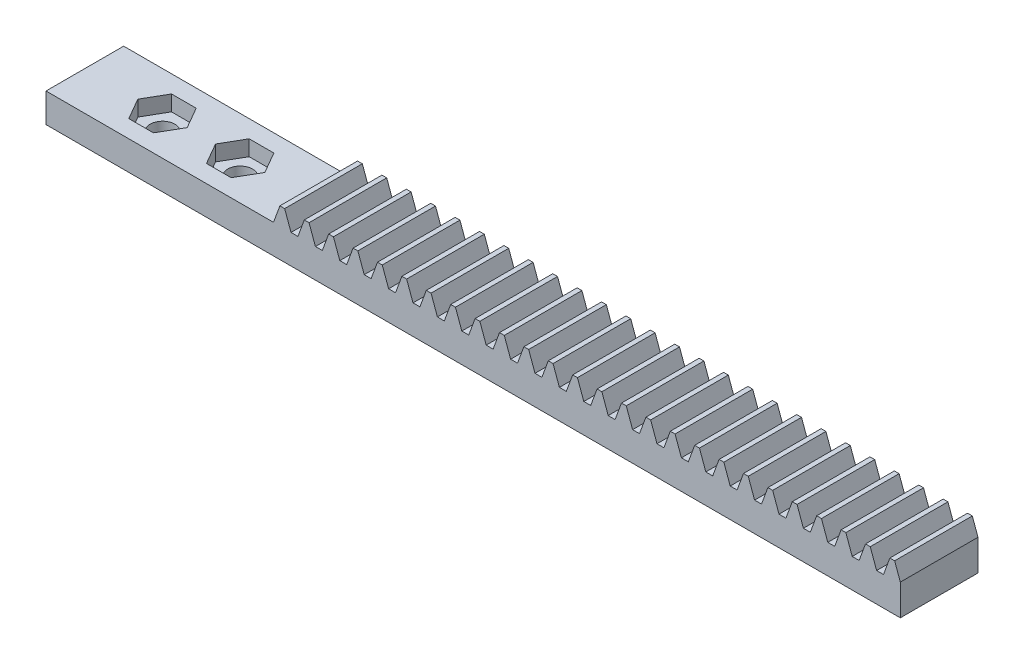
SolidWorks part; units mm, degrees
extrude "Blank" add sketch "BlankSke" against normal blind 10
sketch "BlankSke" plane through (0, 0, 0) normal (0, 0, 1) x (1, 0, 0)
  line L1 (0, 0) -> (100, 0)
  line L2 (0, 0) -> (0, 6)
  line L3 (0, 6) -> (100, 6)
  line L4 (100, 0) -> (100, 6)
  dimension "Length" = 100
ref_plane "Plane1" through (0, 0, 0) normal (0, 0, 1) x (1, 0, 0)
ref_plane "Plane2" through (0, 0, 0) normal (0, 1, 0) x (1, 0, 0)
ref_plane "Plane3" through (0, 0, 0) normal (1, 0, 0) x (0, 0, -1)
other "Configuration Table"
sketch "HoldingSke" plane through (0, 0, 0) normal (0, 1, 0) x (1, 0, 0)
  line L0 (0, 0) -> (0.1392, 0.9903)
  line L1 (-15, 0) -> (100, 0) construction
  line L2 (0, 0) -> (-2.1039, 2.3779)
  line L3 (0, 0) -> (-11.863, 4.5341)
  line L4 (0, 0) -> (7.2428, 4.7035)
  line L5 (0, 0) -> (-23.7986, -8.8762)
  line L6 (0, 0) -> (-10.5278, -7.1032)
  line L9 (-71.009, 38.7566) -> (22.9603, 72.9586)
  line L10 (-76.2, 3.3779) -> (-71.2, 3.3779)
  line L11 (0, 0) -> (-10, 0)
  line L12 (-76.2, 101.6) -> (-76.162, 101.6)
  line L13 (24.9733, 27.94) -> (52.9518, 28.4284)
  line L14 (24.9733, 27.94) -> (24.9743, 27.94)
  line L15 (24.9733, 27.94) -> (100.4006, 29.5858)
  circle A0 centre (0, 0) radius 19.05
  circle A1 centre (0, 0) radius 2.5
  circle A2 centre (0, 0) radius 12.7
  dimension "Num_teeth" = 33
  dimension "Width" = 10
  dimension "Length" = 100
  dimension "Pitch_height" = 5
sketch "TooCutSkeIll" plane through (0, 0, 0) normal (0, 0, 1) x (1, 0, 0)
  line L0 (-1.2538, 5.9737) -> (-0.5045, 3.9152)
  line L1 (-0.2687, 3.75) -> (0.2687, 3.75)
  line L2 (0.5045, 3.9152) -> (1.2538, 5.9737)
  line L3 (100, 6) -> (0, 6) construction
  line L4 (0, 0) -> (0, 64.897) construction
  line L5 (-13.208, 5) -> (12.954, 5) construction
  line L6 (0, 0) -> (100, 0) construction
  line L7 (0.8994, 5) -> (0.8994, 48.7463) construction
  line L8 (-0.8994, 5) -> (-0.8994, 48.7463) construction
  line L9 (1.2914, 6) -> (1.2914, 6.0254)
  line L10 (-1.2914, 6) -> (-1.2914, 6.0254)
  line L11 (-1.2914, 6.0254) -> (1.2914, 6.0254)
  arc A0 (0.2687, 3.75) -> (0.5045, 3.9152) centre (0.2687, 4.001) ccw
  arc A1 (-0.5045, 3.9152) -> (-0.2687, 3.75) centre (-0.2687, 4.001) ccw
  arc A2 (1.2914, 6) -> (1.2538, 5.9737) centre (1.2914, 5.96) ccw
  arc A3 (-1.2538, 5.9737) -> (-1.2914, 6) centre (-1.2914, 5.96) ccw
  dimension "Addendum_plus" = 1.0254
  dimension "Pitch_height" = 5
  dimension "Pressure_angle" = 20
  dimension "Gap_width" = 1.7988
  dimension "Dedendum" = 1.25
extrude "ToothCutIll" [suppressed] cut sketch "TooCutSkeIll" against normal through all
sketch "TooCutSkeSim" plane through (0, 0, 0) normal (0, 0, 1) x (1, 0, 0)
  line L0 (0.4444, 3.75) -> (-0.4444, 3.75)
  line L1 (1.2726, 6.0254) -> (0.4444, 3.75)
  line L2 (0, 17.4625) -> (0, 53.467) construction
  line L3 (1.2726, 6.0254) -> (-1.2726, 6.0254)
  line L6 (-1.2726, 6.0254) -> (-0.4444, 3.75)
  line L9 (-0.8994, 5) -> (0.8994, 5) construction
  line L10 (0, 0) -> (100, 0) construction
  line L11 (0.8994, 5) -> (0.8994, 53.467) construction
  line L12 (-0.8994, 5) -> (-0.8994, 53.467) construction
  dimension "Addendum_plus" = 1.0254
  dimension "Pitch_height" = 5
  dimension "Pressure_angle" = 20
  dimension "Gap_width" = 1.7988
  dimension "Dedendum" = 1.25
extrude "ToothCutSim" cut sketch "TooCutSkeSim" against normal through all
pattern_linear "TeethCuts" count 33 spacing 3.1416 along (1, 0, 0) of "ToothCutIll", "ToothCutSim"
sketch "草图1" plane through (0, 0, 0) normal (0, 0, 1) x (1, 0, 0)
  line L1 (0, 3.75) -> (19.294, 3.75)
  line L2 (0, 3.75) -> (0, 13.2211)
  line L3 (0, 13.2211) -> (19.294, 13.2211)
  line L4 (19.294, 3.75) -> (19.294, 13.2211)
extrude "切除-拉伸1" cut sketch "草图1" against normal blind 10
sketch "草图2" plane through (0, 0, 0) normal (-1, 0, 0) x (0, 0, 1)
  line L1 (-10, 3.75) -> (0, 3.75)
  line L2 (-10, 3.75) -> (-10, 0)
  line L3 (-10, 0) -> (0, 0)
  line L4 (0, 3.75) -> (0, 0)
extrude "凸台-拉伸1" add sketch "草图2" along normal blind 10
sketch "草图3" plane through (0, 3.75, 0) normal (0, 1, 0) x (1, 0, 0)
  line L0 (-10, 5) -> (19.294, 5) construction
  line L1 (-10, 0) -> (-10, 10) construction
  line L2 (19.294, 10) -> (19.294, 0) construction
  circle A0 centre (0, 5) radius 1.6
  circle A1 centre (10, 5) radius 1.6
  dimension "D1" = 3.2
  dimension "D2" = 10
  dimension "D3" = 3.2
  dimension "D4" = 10
extrude "切除-拉伸2" cut sketch "草图3" against normal blind 10
sketch "草图4" plane through (0, 3.75, 0) normal (0, 1, 0) x (1, 0, 0)
  line L1 (-1.5877, 7.75) -> (-3.1754, 5)
  line L2 (-3.1754, 5) -> (-1.5877, 2.25)
  line L3 (-1.5877, 2.25) -> (1.5877, 2.25)
  line L4 (1.5877, 2.25) -> (3.1754, 5)
  line L5 (3.1754, 5) -> (1.5877, 7.75)
  line L6 (1.5877, 7.75) -> (-1.5877, 7.75)
  line L7 (8.4123, 7.75) -> (6.8246, 5)
  line L8 (6.8246, 5) -> (8.4123, 2.25)
  line L9 (8.4123, 2.25) -> (11.5877, 2.25)
  line L10 (11.5877, 2.25) -> (13.1754, 5)
  line L11 (13.1754, 5) -> (11.5877, 7.75)
  line L12 (11.5877, 7.75) -> (8.4123, 7.75)
  circle A0 centre (0, 5) radius 2.75 construction
  circle A1 centre (10, 5) radius 2.75 construction
  dimension "D1" = 5.5
  dimension "D2" = 5.5
extrude "切除-拉伸3" cut sketch "草图4" against normal blind 2
equation "' \"Module@HoldingSke\" = 6.35"
equation "' \"Num_teeth@HoldingSke\" = 12"
equation "' \"Ap@HoldingSke\" =  20"
equation "' \"Ap@HoldingSke\" = 20"
equation "' \"Width@HoldingSke\" = 0.25 * 25.4"
equation "' \"Show_teeth@HoldingSke\" = 500"
equation "' \"Backlash@HoldingSke\" = 0.009 * 25.4"
equation "' \"Addendum_fac@HoldingSke\" = 1.0"
equation "' \"Dedendum_fac@HoldingSke\" = 1.25"
equation "' \"Dedendum_add@HoldingSke\" = 0.00005 * 25.4"
equation "' \"Clearance_fac@HoldingSke\" = 0.25"
equation "' \"Pitch_height@HoldingSke\" = 1 * 25.4"
equation "' \"Length@HoldingSke\" = 4.71 * 25.4"
equation "\"Pitch@HoldingSke\" = 1 / \"Module@HoldingSke\""
equation "\"MPH@HoldingSke\" = \"Dedendum_fac@HoldingSke\" / \"Pitch@HoldingSke\" + 2 * \"Dedendum_add@HoldingSke\" + 0.002 * 25.4"
equation "\"MPH@HoldingSke\" = ((sgn( \"MPH@HoldingSke\" - \"Pitch_height@HoldingSke\")+1)*( \"MPH@HoldingSke\" - \"Pitch_height@HoldingSke\"))/2 + \"Pitch_height@HoldingSke\""
equation "\"Blank_height@BlankSke\" = \"Pitch_height@HoldingSke\" + \"Addendum_fac@HoldingSke\"  / \"Pitch@HoldingSke\" "
equation "\"Length@BlankSke\" =  \"Length@HoldingSke\""
equation "\"Face_width@Blank\" = \"Width@HoldingSke\""
equation "\"Pressure_angle@TooCutSkeIll\" = \"Ap@HoldingSke\""
equation "\"Addendum_plus@TooCutSkeIll\" =  \"Addendum_fac@HoldingSke\"  / \"Pitch@HoldingSke\" + 0.001 *25.4"
equation "\"Dedendum@TooCutSkeIll\" = \"Dedendum_fac@HoldingSke\"  / \"Pitch@HoldingSke\""
equation "\"Pitch_height@TooCutSkeIll\" =  \"MPH@HoldingSke\""
equation "\"Gap_width@TooCutSkeIll\" = 3.14159265 / 2 / \"Pitch@HoldingSke\" + 6 * \"Backlash@HoldingSke\""
equation "\"Pressure_angle@TooCutSkeSim\" = \"Ap@HoldingSke\""
equation "\"Addendum_plus@TooCutSkeSim\" =  \"Addendum_fac@HoldingSke\"  / \"Pitch@HoldingSke\" + 0.001 * 25.4"
equation "\"Dedendum@TooCutSkeSim\" = \"Dedendum_fac@HoldingSke\"  / \"Pitch@HoldingSke\""
equation "\"Pitch_height@TooCutSkeSim\" =  \"MPH@HoldingSke\""
equation "\"Gap_width@TooCutSkeSim\" = 3.14159265 / 2 / \"Pitch@HoldingSke\" + 6 * \"Backlash@HoldingSke\""
equation "\"Root_fillet@TooCutSkeIll\" = \"Clearance_fac@HoldingSke\" / \"Pitch@HoldingSke\" + \"Dedendum_add@HoldingSke\""
equation "\"Break_rad@TooCutSkeIll\" = 0.02 / \"Pitch@HoldingSke\" * 2"
equation "\"Linear_pitch@TeethCuts\" = 3.14159265 / \"Pitch@HoldingSke\""
equation "\"Num_teeth@HoldingSke\" = int( ( \"Length@HoldingSke\" + 0 ) / (3.14159265 / \"Pitch@HoldingSke\")) + 0.9999  + 1"
equation " \"Num_teeth@TeethCuts\" = int( \"Show_teeth@HoldingSke\" ) + 1"
equation " \"Num_teeth@TeethCuts\" = ((sgn( \"Num_teeth@TeethCuts\" - \"Num_teeth@HoldingSke\" )-1)*( \"Num_teeth@TeethCuts\" - \"Num_teeth@HoldingSke\" ))/-2+ \"Num_teeth@HoldingSke\""
equation " \"Num_teeth@TeethCuts\" = ((sgn( \"Num_teeth@TeethCuts\" - 2.0)+1)*( \"Num_teeth@TeethCuts\" - 2.0))/2 +2.0"
